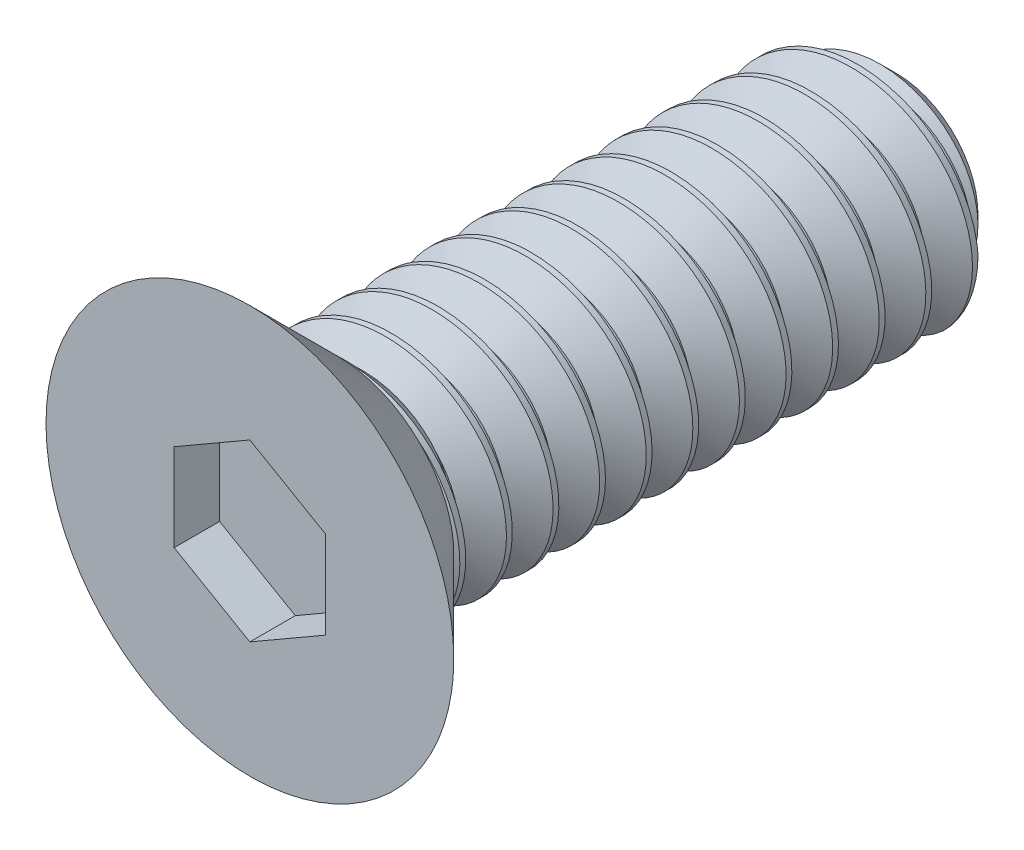
SolidWorks part; units mm, degrees
material "AISI Type 316L stainless steel"
ref_plane "Front" through (0, 0, 0) normal (0, 0, 1) x (1, 0, 0)
ref_plane "Top" through (0, 0, 0) normal (0, 1, 0) x (1, 0, 0)
ref_plane "Right" through (0, 0, 0) normal (1, 0, 0) x (0, 0, -1)
sketch "Sketch1" plane through (0, 0, 0) normal (1, 0, 0) x (0, 0, -1)
  line L0 (0, 2) -> (0.2, 2) construction
  line L1 (0.2, 2) -> (1.2, 1) construction
  line L2 (0, 1) -> (6, 1)
  line L3 (6, 1) -> (6, 0)
  line L4 (6, 0) -> (0, 0)
  line L5 (0, 0) -> (0, 2) construction
  line L6 (0, 2) -> (0, -2) construction
  line L7 (6, 1) -> (6, -1) construction
  line L8 (0, -2) -> (0.2, -2) construction
  line L9 (0.2, -2) -> (1.2, -1) construction
  line L11 (0, 1) -> (0, 0)
  line L12 (1.2, 1) -> (1.2, 0) construction
revolve "Revolve1" add sketch "Sketch1" angle 360 mid plane about L4
sketch "Sketch3" plane through (0, 0, -6) normal (0, 0, -1) x (-1, 0, 0)
  circle A0 centre (0, 0) radius 1
curve "Helix/Spiral1" pitch 0.4 height 6 radius 1 centre (0, 0, -6) axis (0, 0, 1) start towards (0, 1, 0)
sketch "Sketch2" plane through (0, 0, 0) normal (1, 0, 0) x (0, 0, -1)
  line L0 (6, 1) -> (6.35, 1)
  line L1 (6.35, 1) -> (6.2, 0.7402)
  line L2 (6.2, 0.7402) -> (6.15, 0.7402)
  line L3 (6.15, 0.7402) -> (6, 1)
  line L4 (6.075, 0.8701) -> (6.275, 0.8701) construction
  dimension "D1" = 60
  dimension "D2" = 0.05
  dimension "D3" = 0.2
chamfer "Chamfer1" distance 0.3 angle 45 1 edges at (0, 1, -6)
sweep "Cut-Sweep1" cut profiles "Sketch2" path "Helix/Spiral1" align with end faces yes
sketch "Sketch7" plane through (0, 0, 0) normal (1, 0, 0) x (0, 0, -1)
  line L0 (0, 2) -> (0.2, 2) construction
  line L1 (0.2, 2) -> (1.2, 1) construction
  line L2 (0, 2) -> (0.2, 2)
  line L3 (0.2, 2) -> (1.2, 1)
  line L4 (1.2, 1) -> (1.2, 0) construction
  line L5 (1.2, 1) -> (1.2, 0)
  line L7 (0, 0) -> (0, 2) construction
  line L8 (0, 0) -> (0, 2)
  line L9 (0, 0) -> (1.2, 0)
  line L10 (2.2, 0) -> (-2.2, 0) construction
revolve "Revolve2" add sketch "Sketch7" angle 360 mid plane about L9
ref_plane "Plane1" through (0, 0, -1.2) normal (0, 0, 1) x (1, 0, 0)
sketch "Sketch8" plane through (0, 0, -1.2) normal (0, 0, 1) x (1, 0, 0)
  circle A0 centre (0, 0) radius 1
extrude "Boss-Extrude1" add sketch "Sketch8" against normal through all draft 45
sketch "Sketch5" plane through (0, 0, 0) normal (0, 0, 1) x (1, 0, 0)
  line L1 (0.65, -0.3753) -> (0.65, 0.3753)
  line L2 (0.65, 0.3753) -> (0, 0.7506)
  line L3 (0, 0.7506) -> (-0.65, 0.3753)
  line L4 (-0.65, 0.3753) -> (-0.65, -0.3753)
  line L5 (-0.65, -0.3753) -> (0, -0.7506)
  line L6 (0, -0.7506) -> (0.65, -0.3753)
  circle A0 centre (0, 0) radius 0.65 construction
  dimension "Hex" = 1.3
extrude "Cut-Extrude2" cut sketch "Sketch5" against normal blind 0.84
sketch "Sketch6" plane through (0, 0, 0) normal (0, 0, 1) x (1, 0, 0)
  circle A0 centre (0, 0) radius 0.7506
extrude "Cut-Extrude3" cut sketch "Sketch6" against normal blind 0.84 draft 45
sketch "Sketch9" [suppressed] plane through (0, 0, -5.5) normal (0, 0, 1) x (1, 0, 0)
  circle A1 centre (0, 0) radius 5
  circle A2 centre (0, 0) radius 5
  point P0 (0, 5)
  dimension "D1" = 0
extrude "Boss-Extrude2" [suppressed] add sketch "Sketch9" against normal offset from surface (18.5 mm away) 26 up to face at (0, 0.7, -6)
fillet "Fillet1" [suppressed] radius 0.2
sketch "Sketch10" plane through (0, 0, 0) normal (1, 0, 0) x (0, 0, -1)
  line L0 (6, 1) -> (6, -1) construction
  point P0 (5.4, -1)
  dimension "D1" = 0.6
sketch "Sketch11" plane through (0, 0, 0) normal (1, 0, 0) x (0, 0, -1)
  line L1 (0, 0) -> (0.45, 0)
  line L2 (0, 0) -> (0, 2)
  line L3 (0, 2) -> (0.45, 2)
  line L4 (0.45, 0) -> (0.45, 2)
  dimension "D1" = 0.45
revolve "Cut-Revolve1" cut sketch "Sketch11" angle 360 about L1
equation "\"D3@Helix/Spiral1\" = \"Lg@Sketch1\""
equation "\"D2@Sketch2\" = \"D4@Helix/Spiral1\" * .125"
equation "\"D3@Sketch2\" = \"D4@Helix/Spiral1\" * .5"
equation "\"D1@Chamfer1\" = \"D4@Helix/Spiral1\" * .75"
equation "\"D1@Cut-Extrude2\" = \"Head Ht@Sketch1\" * .7"
equation "\"D1@Sketch10\" = \"D4@Helix/Spiral1\" * 1.5"
equation "\"D1@Cut-Extrude3\" = \"D1@Cut-Extrude2\""
equation "\"D1@Fillet1\" = \"Dia@Sketch1\" * .1"
